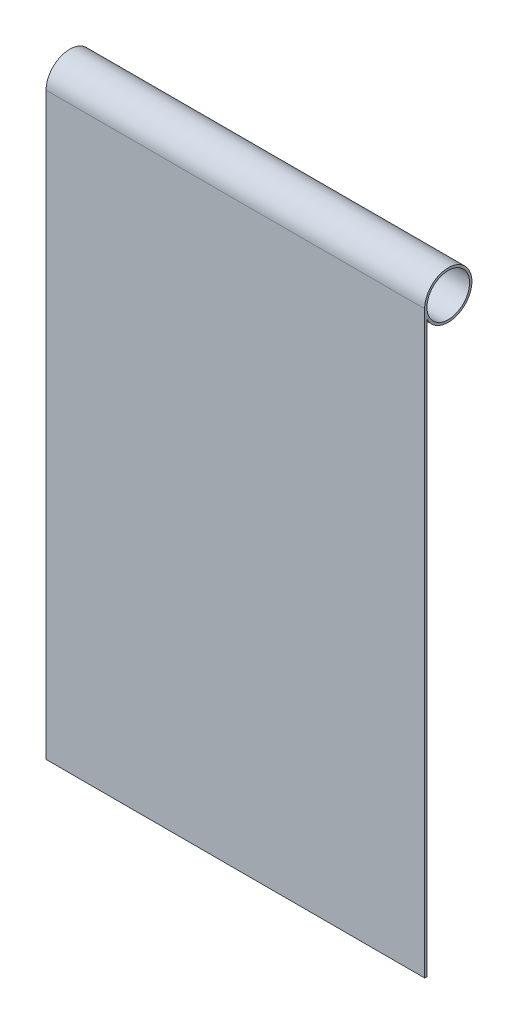
SolidWorks part; units mm, degrees
material "1060 Alloy"
ref_plane "Front Plane" through (0, 0, 0) normal (0, 0, 1) x (1, 0, 0)
ref_plane "Top Plane" through (0, 0, 0) normal (0, 1, 0) x (1, 0, 0)
ref_plane "Right Plane" through (0, 0, 0) normal (1, 0, 0) x (0, 0, -1)
sketch "Sketch1" plane through (0, 0, 0) normal (1, 0, 0) x (0, 0, -1)
  line L0 (-10, 125) -> (-10, -120)
  line L1 (-10, -120) -> (-9, -120)
  line L2 (-9, -120) -> (-9, 120.6411)
  line L3 (0, 0) -> (-33.7224, 0) construction
  arc A0 (-9, 120.6411) -> (-10, 125) centre (0, 125) ccw
  circle A1 centre (0, 125) radius 9
  dimension "D2" = 20
  dimension "D3" = 18
  dimension "D1" = 125
  dimension "D4" = 120
extrude "Boss-Extrude1" add sketch "Sketch1" along normal blind 80 and the other way blind 80
